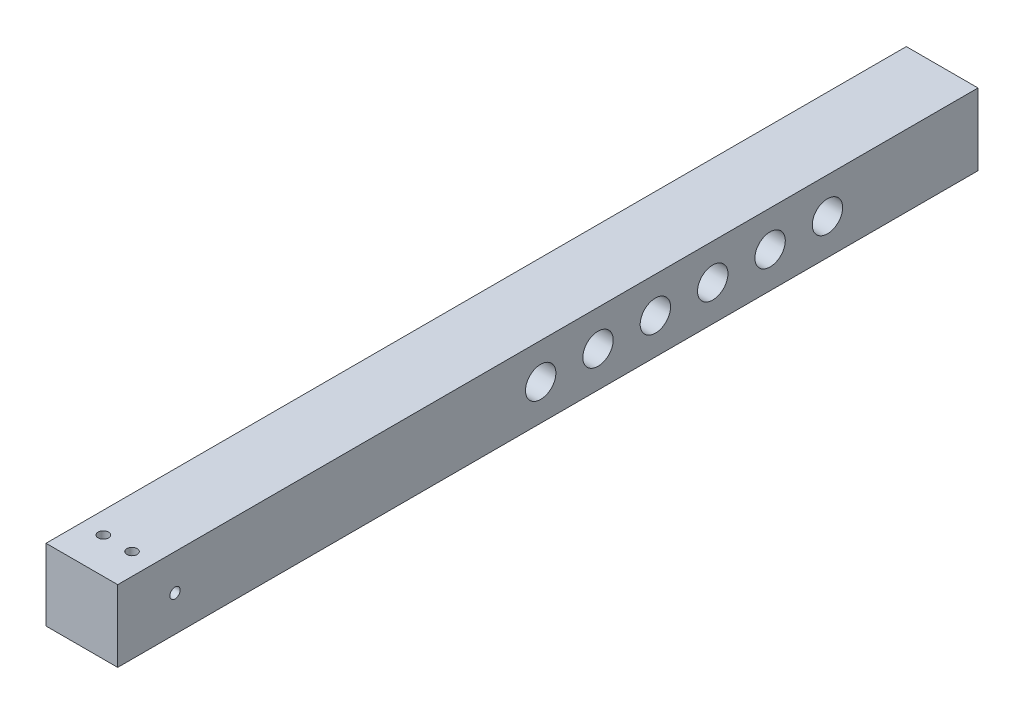
SolidWorks part; units mm, degrees
ref_plane "Front Plane" through (0, 0, 0) normal (0, 0, 1) x (1, 0, 0)
ref_plane "Top Plane" through (0, 0, 0) normal (0, 1, 0) x (1, 0, 0)
ref_plane "Right Plane" through (0, 0, 0) normal (1, 0, 0) x (0, 0, -1)
sketch "Sketch1" plane through (0, 0, 0) normal (0, 0, 1) x (1, 0, 0)
  line L1 (-12.5, 12.5) -> (12.5, 12.5)
  line L2 (-12.5, 12.5) -> (-12.5, -12.5)
  line L3 (-12.5, -12.5) -> (12.5, -12.5)
  line L4 (12.5, 12.5) -> (12.5, -12.5)
  line L5 (-12.5, 12.5) -> (12.5, -12.5) construction
  line L6 (-12.5, -12.5) -> (12.5, 12.5) construction
  point P0 (0, 0)
  dimension "D1" = 25
  dimension "D2" = 25
extrude "Boss-Extrude1" add sketch "Sketch1" along normal blind 200
sketch "Sketch2" plane through (12.5, 0, 0) normal (1, 0, 0) x (0, 0, -1)
  line L0 (-200, -12.5) -> (0, -12.5) construction
  line L1 (0, 12.5) -> (-25, 12.5) construction
  line L2 (0, 12.5) -> (0, -12.5) construction
  line L3 (0, -12.5) -> (-25, -12.5) construction
  line L4 (-25, 12.5) -> (-25, -12.5) construction
  line L5 (0, 12.5) -> (-25, -12.5) construction
  line L6 (0, -12.5) -> (-25, 12.5) construction
  line L7 (0, -12.5) -> (0, 12.5) construction
  circle A0 centre (-12.5, 0) radius 2.5
  point P0 (-12.5, 0)
  dimension "D1" = 25
extrude "Cut-Extrude1" cut sketch "Sketch2" against normal through all
sketch "Sketch3" plane through (0, 12.5, 0) normal (0, 1, 0) x (1, 0, 0)
  line L0 (12.5, -200) -> (-12.5, -200) construction
  line L2 (0, -1000) -> (0, 49000) construction
  circle A0 centre (-5, -187.5) radius 1.8
  circle A1 centre (5, -187.5) radius 1.8
  dimension "D1" = 3.6
  dimension "D2" = 3.6
  dimension "D3" = 12.5
  dimension "D4" = 5
  dimension "D5" = 5
extrude "Cut-Extrude2" cut sketch "Sketch3" against normal through all
sketch "Sketch4" plane through (-12.5, 0, 0) normal (-1, 0, 0) x (0, 0, 1)
  line L0 (200, -12.5) -> (0, -12.5) construction
  line L2 (200, 12.5) -> (200, -12.5) construction
  circle A0 centre (180, 0) radius 1.8
  dimension "D1" = 3.6
  dimension "D3" = 20
  dimension "D2" = 12.5
extrude "Cut-Extrude3" cut sketch "Sketch4" against normal through all both and the other way through all
ref_plane "Plane1" through (0, 0, 12.5) normal (0, 0, -1) x (-1, 0, 0)
mirror "Mirror2" about plane through (0, 0, 12.5) normal (0, 0, -1) of "Cut-Extrude3", "Cut-Extrude2", "Cut-Extrude1", "Boss-Extrude1"
sketch "Sketch6" plane through (12.5, 0, 0) normal (1, 0, 0) x (0, 0, -1)
  line L0 (175, -12.5) -> (175, 12.5) construction
  line L1 (-12.5, -1000) -> (-12.5, 49000) construction
  line L2 (-12.5, 0) -> (7.5, 0) construction
  circle A0 centre (155, 0) radius 1.8 construction
  circle A1 centre (7.5, 0) radius 2.5
  circle A4 centre (-12.5, 0) radius 2.5 construction
  circle A5 centre (-12.5, 0) radius 2.5
  circle A6 centre (27.5, 0) radius 2.5
  circle A7 centre (47.5, 0) radius 2.5
  dimension "D1" = 20
  dimension "D5" = 20
  dimension "D4" = 4
extrude "Cut-Extrude5" cut sketch "Sketch6" against normal through all both and the other way through all
sketch "Sketch7" plane through (-12.5, 0, 0) normal (-1, 0, 0) x (0, 0, 1)
  circle A0 centre (-47.5, 0) radius 5.3
  circle A1 centre (-27.5, 0) radius 5.3
  circle A2 centre (-7.5, 0) radius 5.3
  circle A3 centre (12.5, 0) radius 5.3
  circle A4 centre (52.5, 0) radius 5.3
  circle A5 centre (32.5, 0) radius 5.3
  point P13 (32.6908, -0.9045)
  point P14 (58.21, -0.9045)
  point P15 (0, 0)
  dimension "D1" = 10.6
  dimension "D3" = 20
  dimension "D4" = 20
  dimension "D5" = 20
  dimension "D6" = 10.6
  dimension "D7" = 10.6
  dimension "D2" = 4
extrude "Cut-Extrude6" cut sketch "Sketch7" against normal through all both and the other way through all
sketch "Sketch8" plane through (-12.5, 0, 0) normal (-1, 0, 0) x (0, 0, 1)
  line L0 (200, 12.5) -> (-175, 12.5) construction
  line L1 (-175, -12.5) -> (-100, -12.5)
  line L2 (-175, -12.5) -> (-175, 12.5)
  line L3 (-175, 12.5) -> (-100, 12.5)
  line L4 (-100, -12.5) -> (-100, 12.5)
  dimension "D1" = 75
extrude "Cut-Extrude7" cut sketch "Sketch8" against normal through all both and the other way through all
